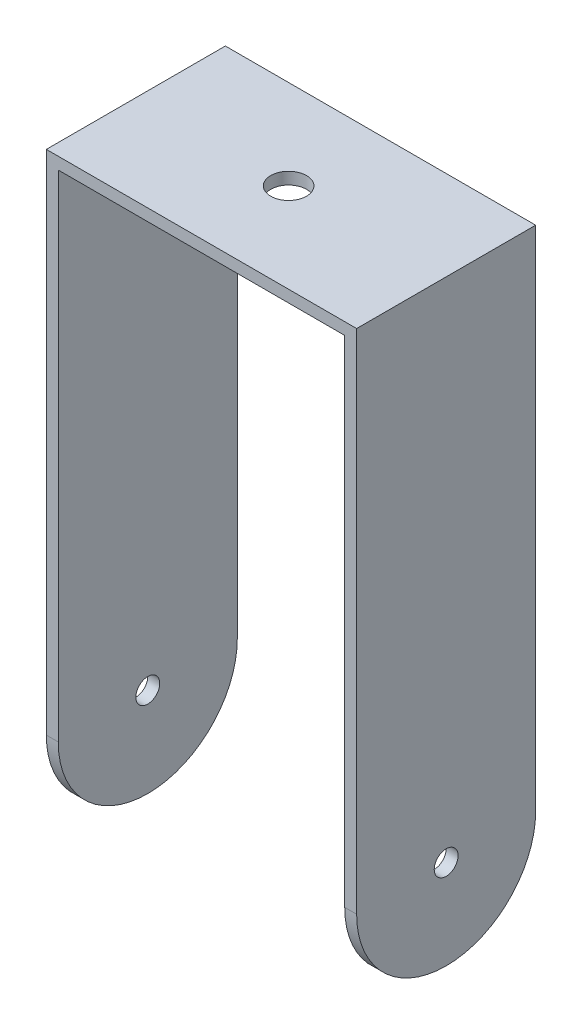
SolidWorks part; units mm, degrees
ref_plane "Front Plane" through (0, 0, 0) normal (0, 0, 1) x (1, 0, 0)
ref_plane "Top Plane" through (0, 0, 0) normal (0, 1, 0) x (1, 0, 0)
ref_plane "Right Plane" through (0, 0, 0) normal (1, 0, 0) x (0, 0, -1)
sketch "Sketch1" plane through (0, 0, 0) normal (0, 0, 1) x (1, 0, 0)
  line L0 (125, -250) -> (130, -250)
  line L1 (0, 0) -> (130, 0)
  line L2 (0, 0) -> (0, -250)
  line L3 (0, -250) -> (5, -250)
  line L4 (130, 0) -> (130, -250)
  line L5 (5, -5) -> (125, -5)
  line L6 (5, -5) -> (5, -250)
  line L8 (125, -5) -> (125, -250)
  dimension "D1" = 250
  dimension "D2" = 130
  dimension "D3" = 5
  dimension "D4" = 5
  dimension "D5" = 5
extrude "Boss-Extrude1" add sketch "Sketch1" along normal blind 75
sketch "Sketch2" plane through (0, 0, 0) normal (0, 1, 0) x (1, 0, 0)
  line L0 (130, -75) -> (130, 0) construction
  line L1 (130, -75) -> (0, -75) construction
  circle A1 centre (64, -37.5) radius 7.5
  dimension "D1" = 66
  dimension "D2" = 37.5
extrude "Cut-Extrude1" cut sketch "Sketch2" against normal blind 8
sketch "Sketch3" plane through (130, 0, 0) normal (1, 0, 0) x (0, 0, -1)
  line L0 (-75, -250) -> (0, -250) construction
  line L1 (-75, -250) -> (-75, 0) construction
  circle A0 centre (-37.5, -212.5) radius 5
  dimension "D3" = 10
  dimension "D1" = 37.5
  dimension "D2" = 37.5
extrude "Cut-Extrude2" cut sketch "Sketch3" against normal blind 134
fillet "Fillet1" radius 37.5 4 edges at (127.5, -250, 75) (2.5, -250, 75) (2.5, -250, 0) (127.5, -250, 0)
